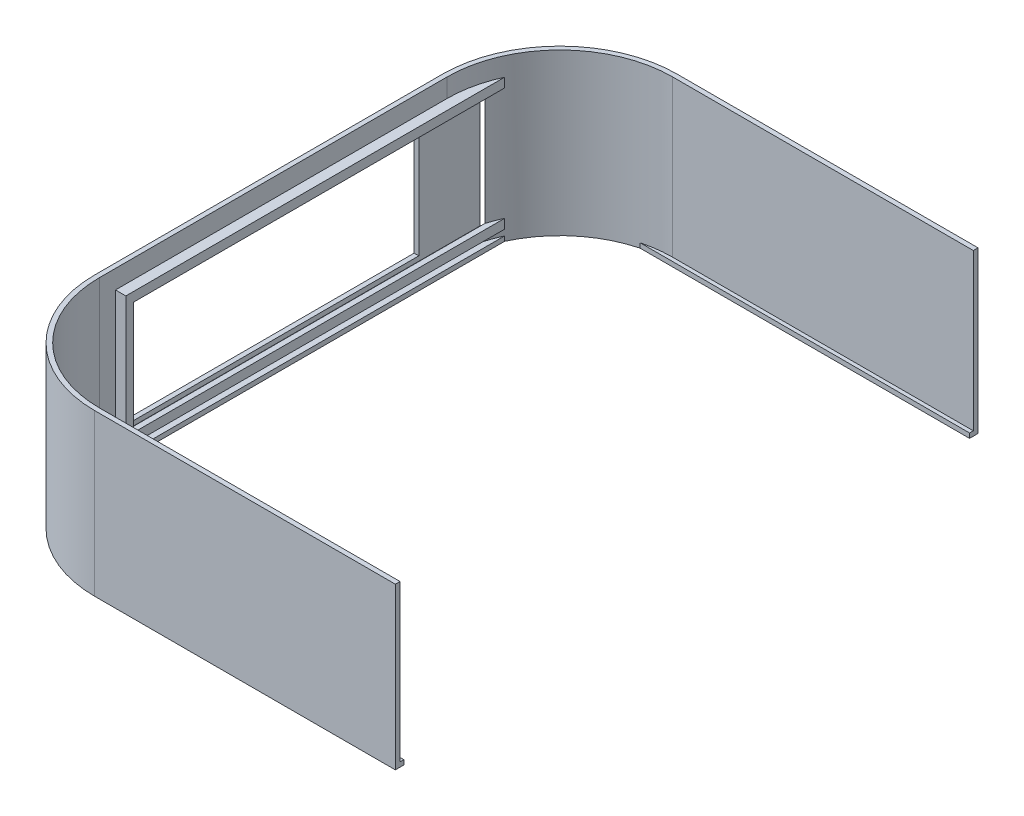
SolidWorks part; units mm, degrees
ref_plane "Alzado" through (0, 0, 0) normal (0, 0, 1) x (1, 0, 0)
ref_plane "Planta" through (0, 0, 0) normal (0, 1, 0) x (1, 0, 0)
ref_plane "Vista lateral" through (0, 0, 0) normal (1, 0, 0) x (0, 0, -1)
sketch "Croquis1" plane through (0, 0, 0) normal (0, 1, 0) x (1, 0, 0)
  line L0 (0, 152.5) -> (0, 80) construction
  line L1 (0, 80) -> (-70, 80) construction
  line L2 (-70, 80) -> (-70, -80) construction
  line L3 (-70, -80) -> (0, -80) construction
  line L4 (0, -80) -> (0, -152.5) construction
  line L5 (0, -152.5) -> (-150, -152.5) construction
  line L6 (-150, -152.5) -> (-150, 152.5) construction
  line L7 (-150, 152.5) -> (0, 152.5) construction
  line L8 (70, -152.55) -> (-150.05, -152.55)
  line L9 (-150.05, -152.55) -> (-150.05, 152.55)
  line L10 (-150.05, 152.55) -> (70, 152.55)
  line L11 (70, 152.55) -> (70, 155.05)
  line L12 (70, 155.05) -> (-152.55, 155.05)
  line L13 (-152.55, 155.05) -> (-152.55, -155.05)
  line L14 (-152.55, -155.05) -> (70, -155.05)
  line L15 (70, -155.05) -> (70, -152.55)
  point P9 (-70, 0)
  point P10 (-150, 0)
  point P17 (70, -153.8)
  dimension "D1" = 305
  dimension "D2" = 160
  dimension "D3" = 70
  dimension "D4" = 150
  dimension "D5" = 0.05
  dimension "D6" = 0.05
  dimension "D7" = 0.05
  dimension "D8" = 2.5
  dimension "D9" = 2.5
  dimension "D10" = 140
extrude "Saliente-Extruir1" add sketch "Croquis1" along normal blind 83.1
fillet "Redondeo1" radius 60 2 edges at (-150.05, 41.55, 152.55) (-150.05, 41.55, -152.55)
sketch "Croquis2" plane through (0, 0, 0) normal (0, -1, 0) x (1, 0, 0)
  line L0 (70, -155.05) -> (-152.55, -155.05) construction
  line L1 (-152.55, -155.05) -> (-152.55, 155.05) construction
  line L2 (-152.55, 155.05) -> (70, 155.05) construction
  line L3 (70, -155.05) -> (-152.55, -155.05)
  line L4 (-152.55, -155.05) -> (-152.55, 155.05)
  line L5 (-152.55, 155.05) -> (70, 155.05)
  line L6 (70, 155.05) -> (70, 150.55)
  line L7 (70, 150.55) -> (-105.4123, 150.55)
  line L8 (-144.55, 117.6448) -> (-144.55, -117.6448)
  line L9 (-105.4123, -150.55) -> (70, -150.55)
  line L10 (70, -150.55) -> (70, -155.05)
  arc A0 (-105.4123, 150.55) -> (-144.55, 117.6448) centre (-90.05, 92.55) ccw
  arc A1 (-144.55, -117.6448) -> (-105.4123, -150.55) centre (-90.05, -92.55) ccw
  dimension "D2" = 4.5
extrude "Saliente-Extruir2" add sketch "Croquis2" along normal blind 2.5
ref_plane "Plano1" through (0, 3.1, 0) normal (0, 1, 0) x (1, 0, 0)
sketch "Croquis5" plane through (0, 3.1, 0) normal (0, 1, 0) x (1, 0, 0)
  line L0 (70, -152.55) -> (-90.05, -152.55) construction
  line L1 (-150.05, 155.05) -> (-144.55, 155.05)
  line L2 (-150.05, 155.05) -> (-150.05, -152.55)
  line L3 (-150.05, -152.55) -> (-144.55, -152.55)
  line L4 (-144.55, 155.05) -> (-144.55, -152.55)
  line L5 (-150.05, 155.05) -> (-144.55, -152.55) construction
  line L6 (-150.05, -152.55) -> (-144.55, 155.05) construction
  line L7 (-144.55, 117.6448) -> (-144.55, -117.6448) construction
  line L8 (-150.05, -92.55) -> (-150.05, 92.55) construction
  line L9 (70, 155.05) -> (-152.55, 155.05) construction
  point P4 (-147.3, 1.25)
  point P10 (-157.5941, 73.26)
  point P11 (-170.3924, 72.3235)
  point P14 (0, 0)
extrude "Saliente-Extruir4" add sketch "Croquis5" along normal blind 5
sketch "Croquis6" plane through (0, 0, -155.05) normal (0, 0, -1) x (-1, 0, 0)
  line L0 (152.55, 83.1) -> (152.55, -2.5) construction
  line L1 (150.05, 5.65) -> (147.45, 5.65)
  line L2 (150.05, 5.65) -> (150.05, 70.65)
  line L3 (150.05, 70.65) -> (147.45, 70.65)
  line L4 (147.45, 5.65) -> (147.45, 70.65)
  line L5 (150.05, 5.65) -> (147.45, 70.65) construction
  line L6 (150.05, 70.65) -> (147.45, 5.65) construction
  line L8 (144.55, 3.1) -> (150.05, 3.1) construction
  point P4 (148.75, 38.15)
  dimension "D1" = 2.5
  dimension "D2" = 2.6
  dimension "D3" = 2.55
  dimension "D4" = 65
extrude "Cortar-Extruir2" cut sketch "Croquis6" against normal blind 235
sketch "Croquis7" plane through (-152.55, 0, 0) normal (-1, 0, 0) x (0, 0, 1)
  line L0 (1.1, 3.1) -> (-1.1, 3.1) construction
  line L1 (-77.5, 68.15) -> (77.5, 68.15)
  line L2 (-77.5, 68.15) -> (-77.5, 8.15)
  line L3 (-77.5, 8.15) -> (77.5, 8.15)
  line L4 (77.5, 68.15) -> (77.5, 8.15)
  line L5 (-77.5, 68.15) -> (77.5, 8.15) construction
  line L6 (-77.5, 8.15) -> (77.5, 68.15) construction
  point P0 (0, 38.15)
  dimension "D1" = 5.05
  dimension "D2" = 60
  dimension "D3" = 155
extrude "Cortar-Extruir3" cut sketch "Croquis7" against normal blind 3
sketch "Croquis8" plane through (-150.05, 0, 0) normal (1, 0, 0) x (0, 0, -1)
  line L1 (-83.95, 72.1) -> (-79.95, 72.1)
  line L2 (-83.95, 72.1) -> (-83.95, 8.1)
  line L3 (-83.95, 8.1) -> (-79.95, 8.1)
  line L4 (-79.95, 72.1) -> (-79.95, 8.1)
  line L5 (-83.95, 72.1) -> (-79.95, 8.1) construction
  line L6 (-83.95, 8.1) -> (-79.95, 72.1) construction
  point P0 (-81.95, 40.1)
  dimension "D1" = 64
  dimension "D2" = 4
extrude "Saliente-Extruir5" add sketch "Croquis8" along normal up to surface (5.5 mm away) up to face at (-144.55, 5.6, 0)
sketch "Croquis9" plane through (0, 0, -152.55) normal (0, 0, 1) x (1, 0, 0)
  line L0 (-150.05, 70.65) -> (-147.45, 70.65)
  line L1 (-147.45, 70.65) -> (-147.45, 68.2)
  line L2 (-147.45, 68.2) -> (-144.55, 68.2)
  line L3 (-144.55, 68.2) -> (-144.55, 73.15)
  line L4 (-144.55, 73.15) -> (-150.05, 73.15)
  line L5 (-150.05, 83.1) -> (-150.05, 70.65) construction
  line L6 (-150.05, 73.15) -> (-150.05, 70.65)
  line L7 (-147.45, 70.65) -> (-147.45, 8.1) construction
  line L8 (-150.05, 8.15) -> (-150.05, 68.15) construction
  line L9 (-144.55, 8.1) -> (-147.45, 8.1) construction
  point P11 (0, 0)
  dimension "D1" = 2.45
  dimension "D2" = 2.5
extrude "Saliente-Extruir9" add sketch "Croquis9" along normal up to surface (236.5 mm away) up to face at (-147.3, 40.1, 83.95)
sketch "Croquis11" plane through (0, 0, -155.05) normal (0, 0, -1) x (-1, 0, 0)
  line L1 (115.7008, 58.6484) -> (135.7008, 58.6484)
  line L2 (115.7008, 58.6484) -> (115.7008, 46.6484)
  line L3 (115.7008, 46.6484) -> (135.7008, 46.6484)
  line L4 (135.7008, 58.6484) -> (135.7008, 46.6484)
  line L5 (115.7008, 58.6484) -> (135.7008, 46.6484) construction
  line L6 (115.7008, 46.6484) -> (135.7008, 58.6484) construction
  line L7 (115.7008, 31.8834) -> (135.7008, 31.8834)
  line L8 (115.7008, 31.8834) -> (115.7008, 19.8834)
  line L9 (115.7008, 19.8834) -> (135.7008, 19.8834)
  line L10 (135.7008, 31.8834) -> (135.7008, 19.8834)
  line L11 (115.7008, 31.8834) -> (135.7008, 19.8834) construction
  line L12 (115.7008, 19.8834) -> (135.7008, 31.8834) construction
  point P0 (125.7008, 52.6484)
  point P5 (125.7008, 25.8834)
  dimension "D1" = 12
  dimension "D2" = 20
extrude "Cortar-Extruir4" cut sketch "Croquis11" against normal blind 2.5
sketch "Croquis12" plane through (0, 83.1, 0) normal (0, 1, 0) x (1, 0, 0)
  line L0 (-152.55, -92.55) -> (-152.55, -155.05)
  line L1 (-152.55, -155.05) -> (-90.05, -155.05)
  line L2 (-152.55, 92.55) -> (-152.55, 155.05)
  line L3 (-152.55, 155.05) -> (-90.05, 155.05)
  arc A0 (-90.05, 155.05) -> (-152.55, 92.55) centre (-90.05, 92.55) ccw
  arc A1 (-152.55, -92.55) -> (-90.05, -155.05) centre (-90.05, -92.55) ccw
  arc A2 (-150.05, -92.55) -> (-90.05, -152.55) centre (-90.05, -92.55) ccw construction
  arc A3 (-90.05, 152.55) -> (-150.05, 92.55) centre (-90.05, 92.55) ccw construction
  dimension "D1" = 2.5
  dimension "D2" = 2.5
extrude "Cortar-Extruir5" cut sketch "Croquis12" against normal through all
equation "\"D1@Croquis1\"=\"ancho_tot\"-(\"GROSOR_PARED_IMPRESION\"*2)"
equation "\"venesta\"= 4'grosor de la venesta"
equation "\"policarbonato\"= 4'grosor del policarbonato"
equation "\"carton_trupan\"= 3'grosor del carton trupan caso laser"
equation "\"ancho_tot\"= 310'ancho tot sin llantas"
equation "\"largo_tot\"= 400'largo tot sin camera"
equation "\"alto_estimado\"= 300'alto estimado sin lidar"
equation "\"altoparaqpaselabotella\"= 75'alto estimado para que encaje la botella"
equation "\"alturaruedaloca\"= 22"
equation "\"anchoruedaloca\"= 35"
equation "\"anchopiso1motorybaterias\"= 150"
equation "\"dist-pisorampa\"= 5"
equation "\"anchoultimopiso\"= 170"
equation "\"paredtrasera\"= 100"
equation "\"agarradorcanasta\"= 275'recolector"
equation "\"alturapiso1y2\"= 80"
equation "\"alturapiso2y3\"= 80"
equation "\"GROSOR_PARED_IMPRESION\"= 2.5"
equation "\"TOLERANCIA\"= 0.05"
equation "\"D5@Croquis1\"=\"TOLERANCIA\""
equation "\"D6@Croquis1\"=\"TOLERANCIA\""
equation "\"D7@Croquis1\"=\"TOLERANCIA\""
equation "\"D8@Croquis1\"=\"GROSOR_PARED_IMPRESION\""
equation "\"D9@Croquis1\"=\"GROSOR_PARED_IMPRESION\""
equation "\"D10@Croquis1\"= \"apertura\" * 2"
equation "\"apertura\"= 70"
equation "\"D1@Saliente-Extruir2\"=\"GROSOR_PARED_IMPRESION\""
equation "\"D2@Croquis2\"=\"GROSOR_PARED_IMPRESION\"+2"
equation "\"D1@Saliente-Extruir1\"=\"TOLERANCIA\"+\"carton_trupan\"+\"TOLERANCIA\"+\"alturapiso1y2\""
equation "\"D1@Croquis6\"=\"GROSOR_PARED_IMPRESION\""
equation "\"D2@Croquis6\"=\"GROSOR_PARED_IMPRESION\"+\"TOLERANCIA\"*2"
equation "\"D3@Croquis6\"=\"GROSOR_PARED_IMPRESION\"+\"TOLERANCIA\""
equation "\"D1@Croquis7\"=\"GROSOR_PARED_IMPRESION\"+\"TOLERANCIA\"+\"GROSOR_PARED_IMPRESION\""
equation "\"D1@Cortar-Extruir2\"=\"ancho_tot\"-75"
